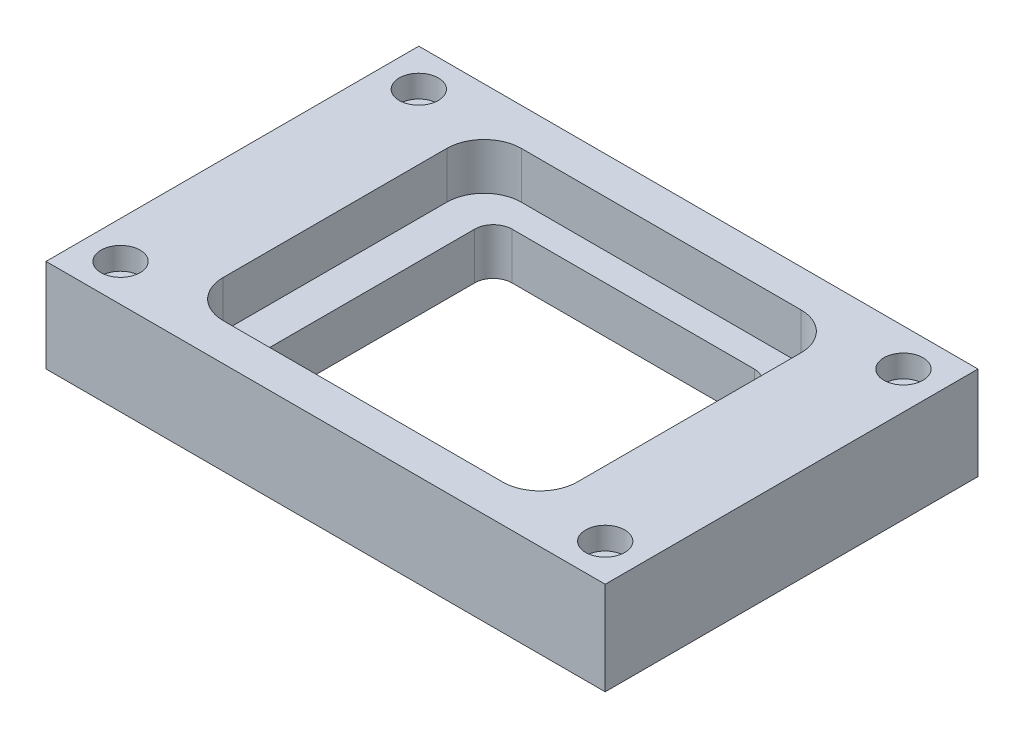
SolidWorks part; units mm, degrees
ref_plane "Alzado" through (0, 0, 0) normal (0, 0, 1) x (1, 0, 0)
ref_plane "Planta" through (0, 0, 0) normal (0, 1, 0) x (1, 0, 0)
ref_plane "Vista lateral" through (0, 0, 0) normal (1, 0, 0) x (0, 0, -1)
sketch "Croquis1" plane through (0, 0, 0) normal (0, 1, 0) x (1, 0, 0)
  line L1 (-150, 100) -> (150, 100)
  line L2 (-150, 100) -> (-150, -100)
  line L3 (-150, -100) -> (150, -100)
  line L4 (150, 100) -> (150, -100)
  line L5 (-150, 100) -> (150, -100) construction
  line L6 (-150, -100) -> (150, 100) construction
  point P0 (0, 0)
  dimension "D1" = 300
  dimension "D2" = 200
extrude "Saliente-Extruir1" add sketch "Croquis1" along normal blind 50
hole_wizard "Taladro1" positions "Croquis2" profile "Croquis3" legacy
sketch "Croquis2" plane through (0, 50, 0) normal (0, 1, 0) x (1, 0, 0)
  point P0 (-130, 80)
  dimension "D1" = 130
  dimension "D2" = 80
sketch "Croquis3" plane through (-130, 50, -80) normal (1, 0, 0) x (0, 0, 1)
  line L0 (0, 0) -> (0, 50.8011)
  line L1 (0, 50.8011) -> (6, 50.8011)
  line L2 (6, 50.8011) -> (6, 12)
  line L3 (6, 12) -> (10.5, 12)
  line L4 (10.5, 12) -> (10.5, 0)
  line L5 (10.5, 0) -> (0, 0)
  line L6 (0, 110) -> (0, -10) construction
  dimension "Diámetro" = 12
  dimension "Profundidad" = 51
  dimension "Diámetro de refrentado 1" = 21
  dimension "Profundidad de refrentado 1" = 12
mirror "Simetría1" about plane through (0, 0, 0) normal (1, 0, 0) of "Taladro1"
mirror "Simetría2" about plane through (0, 0, 0) normal (0, 0, 1) of "Simetría1"
sketch "Croquis4" plane through (0, 50, 0) normal (0, 1, 0) x (1, 0, 0)
  line L1 (-75, 80) -> (75, 80)
  line L2 (-95, 60) -> (-95, -60)
  line L3 (-75, -80) -> (75, -80)
  line L4 (95, 60) -> (95, -60)
  line L5 (-95, 80) -> (95, -80) construction
  line L6 (-95, -80) -> (95, 80) construction
  line L7 (-65, 65) -> (65, 65)
  line L8 (-75, 55) -> (-75, -55)
  line L9 (-65, -65) -> (65, -65)
  line L10 (75, 55) -> (75, -55)
  line L11 (-75, 65) -> (75, -65) construction
  line L12 (-75, -65) -> (75, 65) construction
  arc A0 (-75, -55) -> (-65, -65) centre (-65, -55) ccw
  arc A1 (65, -65) -> (75, -55) centre (65, -55) ccw
  arc A2 (75, 55) -> (65, 65) centre (65, 55) ccw
  arc A3 (-65, 65) -> (-75, 55) centre (-65, 55) ccw
  arc A4 (-95, -60) -> (-75, -80) centre (-75, -60) ccw
  arc A5 (75, -80) -> (95, -60) centre (75, -60) ccw
  arc A6 (75, 80) -> (95, 60) centre (75, 60) cw
  arc A7 (-75, 80) -> (-95, 60) centre (-75, 60) ccw
  point P0 (0, 0)
  point P6 (0, 0)
  dimension "D5" = 10
  dimension "D6" = 20
  dimension "D1" = 190
  dimension "D2" = 150
  dimension "D3" = 160
  dimension "D4" = 130
extrude "Cortar-Extruir1" cut sketch "Croquis4" against normal blind 25
extrude "Cortar-Extruir2" cut sketch "Croquis4<2>" against normal blind 51 contours L7 A3 L8 A0 L9 A1 L10 A2 region at (0, 50, 0)
sketch "Croquis4<2>" plane through (0, 50, 0) normal (0, 1, 0) x (1, 0, 0) same geometry as "Croquis4"
